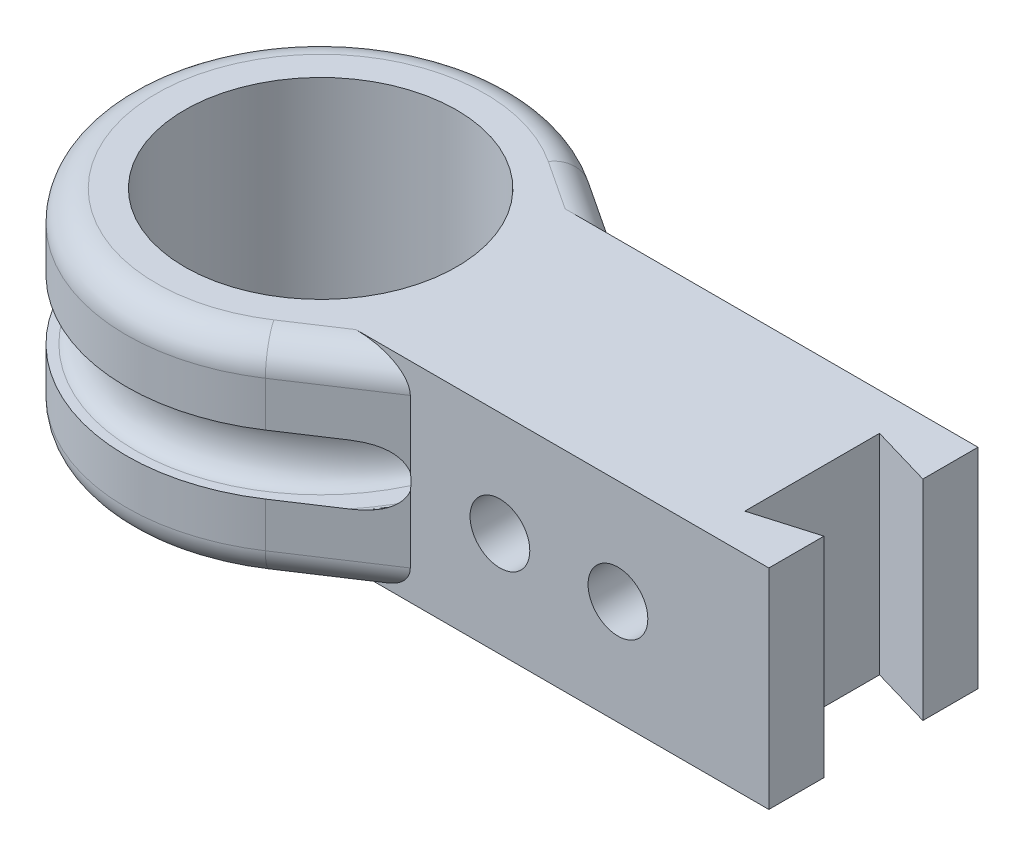
SolidWorks part; units mm, degrees
ref_plane "Front Plane" through (0, 0, 0) normal (0, 0, 1) x (1, 0, 0)
ref_plane "Top Plane" through (0, 0, 0) normal (0, 1, 0) x (1, 0, 0)
ref_plane "Right Plane" through (0, 0, 0) normal (1, 0, 0) x (0, 0, -1)
sketch "Sketch1" plane through (0, 0, 0) normal (0, 1, 0) x (1, 0, 0)
  line L0 (-10.3258, 0) -> (22.3498, 0) construction
  line L1 (6.5, 3.5) -> (3.578, 5.4266)
  line L2 (6.5, -3.5) -> (18.5, -3.5)
  line L4 (6.5, 3.5) -> (18.5, 3.5)
  line L5 (18.5, -3.5) -> (18.5, -1.655)
  line L6 (6.5, -3.5) -> (18.5, 3.5) construction
  line L7 (6.5, 3.5) -> (18.5, -3.5) construction
  line L8 (6.5, -3.5) -> (3.578, -5.4266)
  line L9 (18.5, 1.655) -> (16.45, 2.255)
  line L13 (16.45, -2.255) -> (16.45, 2.255)
  line L16 (16.45, -2.255) -> (18.5, -1.655)
  line L17 (18.5, 1.655) -> (18.5, 3.5)
  arc A0 (3.578, 5.4266) -> (3.578, -5.4266) centre (0, 0) ccw
  circle A1 centre (0, 0) radius 4.55
  point P5 (12.5, 0)
  point P11 (18.5, 0)
  point P18 (18.5, 1.655)
  point P19 (18.5, 2.255)
  point P23 (18.5, -1.655)
  dimension "D1" = 13
  dimension "D2" = 9.1
  dimension "D3" = 12
  dimension "D4" = 7
  dimension "D7" = 0.6
extrude "Boss-Extrude2" add sketch "Sketch1" along normal blind 7 contours A1 | L2 L5 L16 L13 L9 L17 L4 L1 A0 L8 region at (0, 0, 0)
sketch "Sketch2" plane through (0, 0, 0) normal (1, 0, 0) x (0, -1, 0)
  line L0 (0, -0.6001) -> (0, 7.5244) construction
  line L1 (-4.5, 6.805) -> (-4.5, 6.195)
  line L2 (-2.5, 6.195) -> (-2.5, 6.805)
  line L3 (-7.3353, 0) -> (0.2116, 0) construction
  line L4 (-7.3353, 6.5) -> (0.2116, 6.5) construction
  ellipse E0 centre (-3.5, 6.195) end of major axis (-4.5, 6.195) minor radius 0.6 (-4.5, 6.195) -> (-2.5, 6.195) ccw
  ellipse E1 centre (-3.5, 6.805) end of major axis (-4.5, 6.805) minor radius 0.6 (-4.5, 6.805) -> (-2.5, 6.805) cw
  point P5 (-4.5, 6.5)
  point P6 (-2.5, 6.5)
  point P20 (0, 6.5)
  dimension "D1" = 0.61
  dimension "D2" = 2
  dimension "D3" = 2.5
revolve "Cut-Revolve1" cut sketch "Sketch2" angle 360 about L3
sketch "Sketch3" plane through (0, 0, 3.5) normal (0, 0, 1) x (1, 0, 0)
  line L0 (18.5, 3.5) -> (6.0558, 3.5) construction
  line L1 (18.5, 7) -> (18.5, 0) construction
  line L2 (16.45, 7.1416) -> (16.45, -0.1293) construction
  circle A2 centre (13.45, 3.5) radius 1
  circle A3 centre (9.5, 3.5) radius 1
  point P4 (14.45, 3.5)
  point P5 (13.45, 3.5)
  point P11 (9.5, 3.5)
  point P13 (16.45, 3.5)
  point P14 (0, 0)
  dimension "D1" = 2
  dimension "D3" = 3.95
  dimension "D2" = 3
  dimension "D4" = 2.05
extrude "Cut-Extrude1" cut sketch "Sketch3" against normal up to next contours A3 | A2
fillet "Fillet4" radius 1 6 edges at (5.039, 0, -4.4633) (5.039, 0, 4.4633) (5.039, 7, -4.4633) (5.039, 7, 4.4633) (-6.5, 0, 0) (-6.5, 7, 0)
